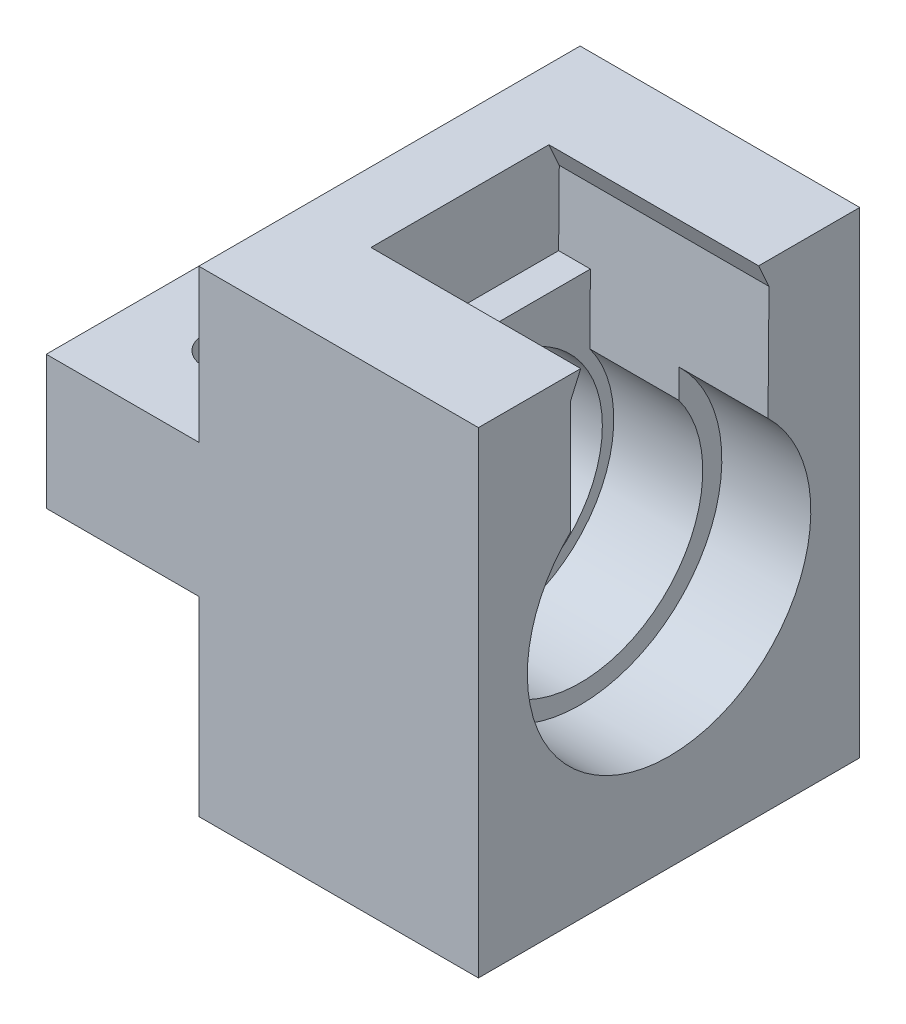
SolidWorks part; units mm, degrees
ref_plane "Спереди" through (0, 0, 0) normal (0, 0, 1) x (1, 0, 0)
ref_plane "Сверху" through (0, 0, 0) normal (0, 1, 0) x (1, 0, 0)
ref_plane "Справа" through (0, 0, 0) normal (1, 0, 0) x (0, 0, -1)
sketch "Эскиз основы" plane through (0, 0, 0) normal (0, 0, 1) x (1, 0, 0)
  line L0 (0, 18.75) -> (0, -18.75)
  line L1 (0, -18.75) -> (-22, -18.75)
  line L2 (-22, -18.75) -> (-22, -3.75)
  line L3 (-22, -3.75) -> (-34, -3.75)
  line L4 (-34, -3.75) -> (-34, 6.75)
  line L5 (-34, 6.75) -> (-22, 6.75)
  line L6 (-22, 6.75) -> (-22, 18.75)
  line L7 (-22, 18.75) -> (0, 18.75)
  point P3 (-20.0562, 11.2374)
  point P10 (0, 0)
  point P11 (-22.6517, 6.75)
  dimension "D1" = 10.5
  dimension "D2" = 12
  dimension "D3" = 15
  dimension "D4" = 12
  dimension "D5" = 22
extrude "Основа" add sketch "Эскиз основы" along normal blind 30
sketch "Эскиз под резистор и подшипник" plane through (0, 0, 0) normal (1, 0, 0) x (0, 0, -1)
  line L7 (-15, 18.75) -> (-15, -18.75) construction
  line L8 (-22.751, 8.75) -> (-7.2109, 8.75)
  line L9 (-21.9532, 18.75) -> (-7.9521, 18.75)
  line L10 (-30, 18.75) -> (0, 18.75) construction
  line L11 (-22.75, 11.15) -> (-7.1899, 11.15)
  line L12 (-30, -18.75) -> (0, -18.75) construction
  line L13 (-30, 0) -> (0, 0) construction
  line L14 (-30, -18.75) -> (-30, 18.75) construction
  line L17 (-7.1392, 16.9402) -> (-7.9521, 18.75)
  line L18 (-7.1392, 16.9402) -> (-7.253, 3.9407)
  line L19 (-22.7476, 16.9472) -> (-22.753, 3.9472)
  line L21 (-22.7476, 16.9472) -> (-21.9532, 18.75)
  circle A0 centre (-15, 0) radius 11.15
  circle A5 centre (-15, 0) radius 7.5838
  circle A6 centre (-15, 0) radius 9.65
  arc A7 (-21.6813, 5.65) -> (-21.6813, -5.65) centre (-15, 0) ccw
  arc A8 (-21.6813, 5.65) -> (-21.6813, -5.65) centre (-15, 0) ccw
  arc A9 (-8.3187, -5.65) -> (-8.3187, 5.65) centre (-15, 0) ccw
  circle A10 centre (-15, 0) radius 8.75
  line M11 (0, 18.75) -> (-30, 18.75)
  dimension "D1" = 22.3
  dimension "D3" = 8.75
  dimension "D5" = 17.5
  dimension "D2" = 1.5
  dimension "D4" = 14.0011
  dimension "D6" = 15.5
  dimension "D7" = 13
extrude "Вырез круглый под резистор" cut sketch "Эскиз2<5>" against normal blind 19 contours A9 A10 A7 A5 | A5 region at (0, 7.7128, 11.4214) region at (0, 0, 15)
sketch "Эскиз2<5>" plane through (0, 0, 0) normal (1, 0, 0) x (0, 0, -1) same geometry as "Эскиз под резистор и подшипник"
extrude "Вырез под участок с проводами" cut sketch "Эскиз2<6>" against normal blind 14 contours A10 L8 A6 L19 A7 | A6 L8 A0 L19 | A10 A9 L18 A6 L8 | A6 L18 A0 L8 | L8 A6 | A6 L8 A0 | A0 L8 L18 L17 L21 L19 M11 | A0 L8 L19 | A0 L18 L8 | A0 L8 L18 L11 | A0 L11 L19 L8 | A6 region at (0, 10.3083, 20.806) region at (0, 8.5091, 22.4758) region at (0, 9.8887, 15) region at (0, 7.7859, 21.5765) region at (0, 14.9126, 14.9548) region at (0, 9.1115, 15) region at (0, 7.1378, 20.3819) region at (0, 10.3041, 9.1627) region at (0, 7.1367, 9.6163) region at (0, 7.778, 8.4106) region at (0, 8.4994, 7.5007)
sketch "Эскиз2<6>" plane through (0, 0, 0) normal (1, 0, 0) x (0, 0, -1) same geometry as "Эскиз под резистор и подшипник"
extrude "Вырез под подшипник" cut sketch "Эскиз под резистор и подшипник" against normal blind 7 contours A6 L19 A0 L18 region at (0, 6.881, 23.0458)
extrude "Вырез-Вытянуть5" cut sketch "Эскиз под резистор и подшипник<7>" against normal blind 16.5 contours A0 L8 L18 L17 L21 L19 M11 region at (0, 14.9126, 14.9548)
sketch "Эскиз под резистор и подшипник<7>" plane through (0, 0, 0) normal (1, 0, 0) x (0, 0, -1) same geometry as "Эскиз под резистор и подшипник"
sketch "Эскиз3" plane through (0, 6.75, 0) normal (0, 1, 0) x (1, 0, 0)
  line L0 (-27, 0) -> (-27, -30) construction
  line L1 (-22, 0) -> (-34, 0) construction
  line L2 (-22, -30) -> (-34, -30) construction
  line L3 (-34, -30) -> (-34, 0) construction
  line L4 (-34, -15) -> (-27, -15) construction
  line L5 (-22, -30) -> (-22, 0) construction
  circle A0 centre (-27, -7.5) radius 2.15
  circle A1 centre (-27, -22.5) radius 2.15
  point P12 (0, 0)
  dimension "D2" = 4.3
  dimension "D1" = 5
  dimension "D3" = 7.5
extrude "Вырез-Вытянуть6" cut sketch "Эскиз3" against normal up to next contours A0 | A1 region at (-27, 6.75, 7.5) region at (-27, 6.75, 22.5)
